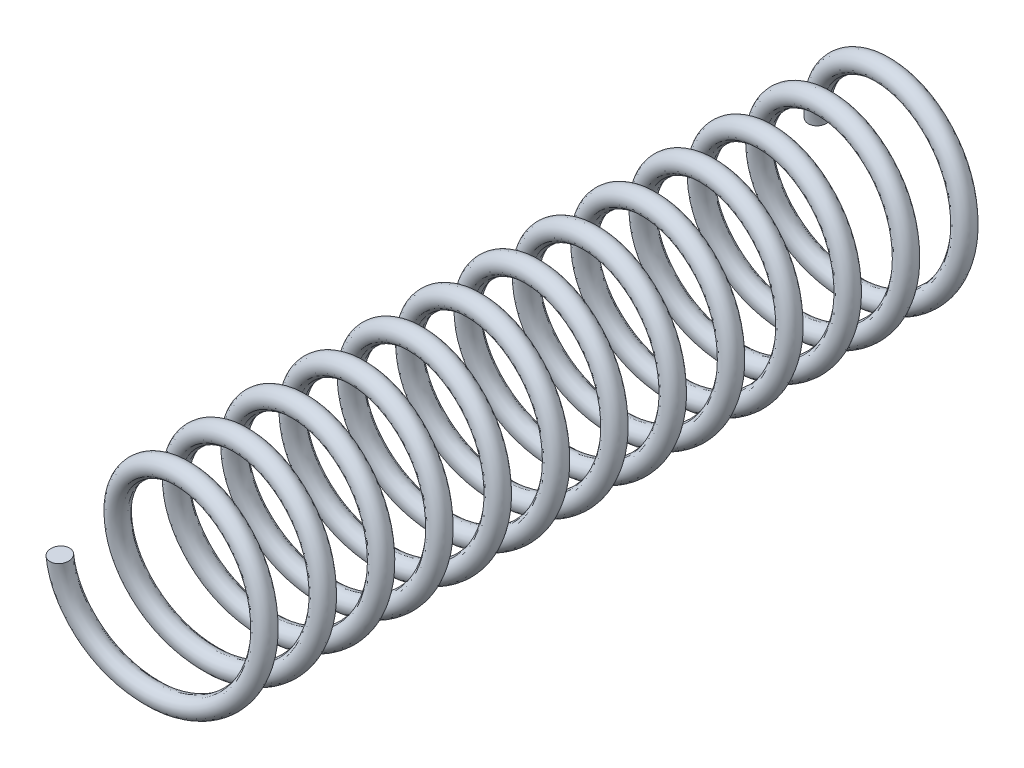
SolidWorks part; units mm, degrees
ref_plane "Front Plane" through (0, 0, 0) normal (0, 0, 1) x (1, 0, 0)
ref_plane "Top Plane" through (0, 0, 0) normal (0, 1, 0) x (1, 0, 0)
ref_plane "Right Plane" through (0, 0, 0) normal (1, 0, 0) x (0, 0, -1)
sketch "Sketch1" plane through (0, 0, 0) normal (0, 0, 1) x (1, 0, 0)
  circle A0 centre (0, 0) radius 1.5
  dimension "D1" = 3
curve "Helix/Spiral1" pitch 1 height 13 radius 1.5 left hand yes centre (0, 0, 0) axis (0, 0, 1) start towards (-1, 0, 0)
ref_plane "Plane1" through (-1.5, 0, 13) normal (0, 0.9944, 0.1055) x (1, 0, 0)
sketch "Sketch2" plane through (-1.5, 0, 13) normal (0, 0.9944, 0.1055) x (1, 0, 0)
  circle A0 centre (0.049, -0.0345) radius 0.5
  dimension "D1" = 1
sketch "Sketch3" plane through (-1.5, 0, 13) normal (0, 0.9944, 0.1055) x (1, 0, 0)
  circle A0 centre (-0.0004, 0.0066) radius 0.1681
sweep "Sweep1" add profiles "Sketch3" path "Helix/Spiral1"
